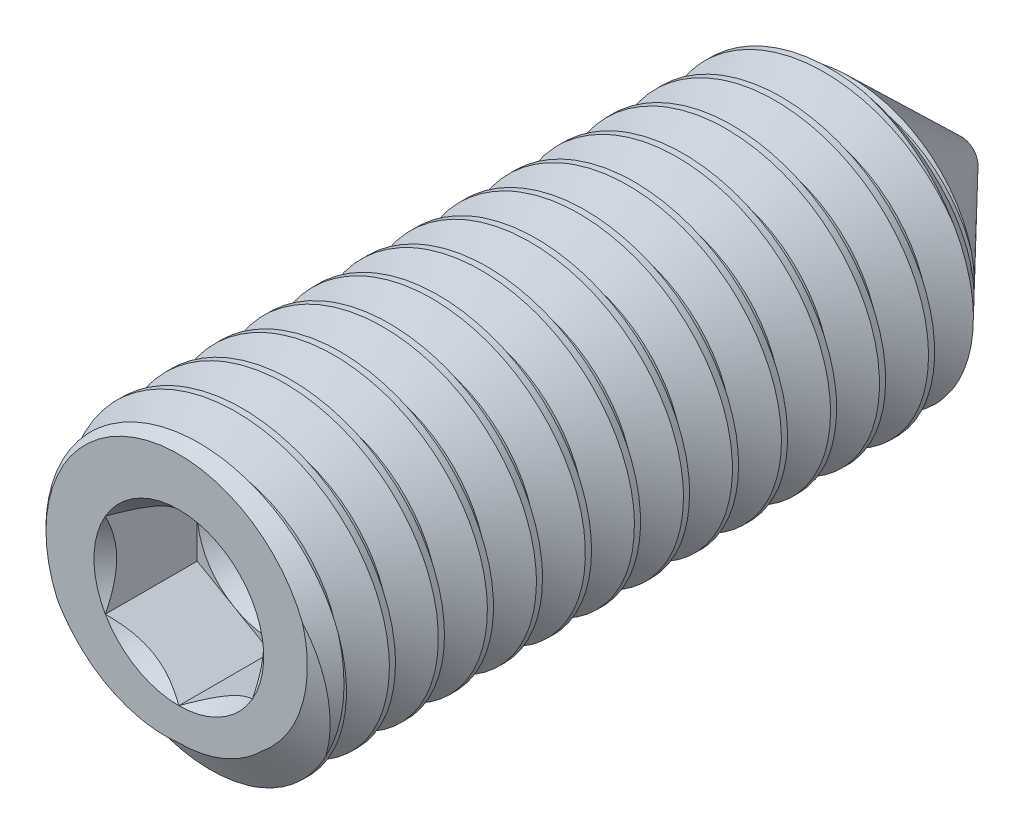
SolidWorks part; units mm, degrees
ref_plane "Front Plane" through (0, 0, 0) normal (0, 0, 1) x (1, 0, 0)
ref_plane "Top Plane" through (0, 0, 0) normal (0, 1, 0) x (1, 0, 0)
ref_plane "Right Plane" through (0, 0, 0) normal (1, 0, 0) x (0, 0, -1)
sketch "Sketch1" plane through (0, 0, 0) normal (1, 0, 0) x (0, 0, -1)
  line L0 (-6.35, 0) -> (6.35, 0) construction
  line L5 (-6.35, 2.413) -> (-6.35, -2.413) construction
  line L6 (6.35, 0.2413) -> (6.35, -0.2413) construction
  line L7 (6.35, 0.2413) -> (4.1783, 2.413) construction
  line L8 (6.35, -0.2413) -> (4.1783, -2.413) construction
  line L9 (-7.0941, 2.4989) -> (-6.3004, 2.4989) construction
  line L10 (-6.3004, 2.4989) -> (-6.6973, 1.8115) construction
  line L11 (-6.6973, 1.8115) -> (-7.0941, 2.4989) construction
  line L12 (-7.0445, 2.413) -> (-6.35, 2.413) construction
  line L13 (-6.7469, 1.8974) -> (-6.6477, 1.8974) construction
  line L14 (-6.6973, 1.8974) -> (-6.6973, 1.8115) construction
  line L15 (-6.6973, 2.413) -> (-6.6973, 2.4989) construction
  point P24 (-6.35, 1.1906)
  point P29 (-4.3656, -2.413)
  dimension "Screw Size Decimal Equivalent" = 4.826
  dimension "Length" = 12.7
  dimension "Cone Point Angle" = 90
  dimension "Drive Size" = 2.3813
  dimension "Approx. Point OD" = 0.4826
  dimension "Thread Pitch" = 0.7937
  dimension "Pitch/8" = 0.0992
  dimension "Thread Note" = 1.9844
sketch "Sketch2" plane through (0, 0, 0) normal (1, 0, 0) x (0, 0, -1)
  line L0 (-6.35, 0) -> (6.35, 0)
  line L1 (6.35, 0) -> (6.35, 0.2413)
  line L2 (6.35, 0.2413) -> (4.1783, 2.413)
  line L3 (4.1783, 2.413) -> (-6.35, 2.413)
  line L4 (-6.35, 2.413) -> (-6.35, 0)
revolve "Revolve1" add sketch "Sketch2" angle 360 about L0
chamfer "Chamfer1" distance 0.2619 angle 45 1 edges at (2.413, 0, 6.35)
sketch "Sketch3" plane through (0, 0, 6.35) normal (0, 0, 1) x (1, 0, 0)
  line L1 (0, -1.3748) -> (1.1906, -0.6874)
  line L2 (1.1906, -0.6874) -> (1.1906, 0.6874)
  line L3 (1.1906, 0.6874) -> (0, 1.3748)
  line L4 (0, 1.3748) -> (-1.1906, 0.6874)
  line L5 (-1.1906, 0.6874) -> (-1.1906, -0.6874)
  line L6 (-1.1906, -0.6874) -> (0, -1.3748)
  circle A0 centre (0, 0) radius 1.1906 construction
  circle A1 centre (0, 0) radius 2.413 construction
extrude "Cut-Extrude1" cut sketch "Sketch3" against normal blind 1.4883
sketch "Sketch4" plane through (0, 0, 6.35) normal (0, 0, 1) x (1, 0, 0)
  circle A0 centre (0, 0) radius 1.3748
extrude "Cut-Extrude2" cut sketch "Sketch4" against normal through all draft 45
sketch "Sketch5" plane through (0, 0, 4.8617) normal (0, 0, 1) x (1, 0, 0)
  line L0 (0, 1.3748) -> (1.1906, 0.6874) construction
  circle A0 centre (0, 0) radius 1.1906
extrude "Cut-Extrude3" cut sketch "Sketch5" against normal through all draft 45
fillet "Fillet1" radius 0.0483 1 edges at (0.2413, 0, -6.35)
sketch "Sketch6" plane through (0, 0, 6.35) normal (0, 0, -1) x (-1, 0, 0)
  circle A0 centre (0, 0) radius 2.413 construction
  circle A1 centre (0, 0) radius 2.413
sketch "Sketch10" plane through (0, 0, 0) normal (1, 0, 0) x (0, 0, -1)
  line L0 (3.7841, 0) -> (6.3359, 0) construction
  line L1 (-6.35, 0) -> (6.35, 0) construction
  line L2 (6.3359, 0) -> (6.3359, 0.2554)
  line L3 (6.3359, 0.2554) -> (4.1016, 2.413)
  line L5 (4.1016, 2.413) -> (3.7841, 2.413) construction
  line L6 (3.7841, 2.413) -> (3.7841, 0) construction
  line L7 (6.3359, 0) -> (6.6534, 0)
  line L8 (6.6534, 0) -> (6.6534, 2.413)
  line L9 (6.6534, 2.413) -> (4.1016, 2.413)
  dimension "D1" = 44
  dimension "D2" = 0.3175
revolve "Cut-Revolve6" cut sketch "Sketch10" angle 360 about L0
curve "Helix/Spiral1" pitch 0.7937 height 13.4937 radius 2.413 centre (0, 0, 6.35) axis (0, 0, -1) start towards (0, 1, 0)
sketch "Sketch7" plane through (0, 0, 0) normal (1, 0, 0) x (0, 0, -1)
  line L6 (-6.7469, 1.8974) -> (-6.6477, 1.8974)
  line L9 (-6.6477, 1.8974) -> (-6.3252, 2.456)
  line L10 (-6.3004, 2.4989) -> (-6.6973, 1.8115) construction
  line L11 (-6.3252, 2.456) -> (-7.0693, 2.456)
  line L12 (-6.6973, 1.8115) -> (-7.0941, 2.4989) construction
  line L13 (-7.0693, 2.456) -> (-6.7469, 1.8974)
  line L14 (-6.6973, 2.413) -> (-6.6973, 2.4989) construction
  point P10 (-6.6973, 2.456)
sweep "Cut-Sweep1" cut profiles "Sketch7" path "Helix/Spiral1" align with end faces yes
fillet "Fillet2" radius 0.0483 1 edges at (0.2554, 0, -6.3359)
equation "\"D1@Chamfer1\"=\"Thread Pitch@Sketch1\" * .33"
equation "\"D1@Cut-Extrude1\"=\"Drive Size@Sketch1\"*.625"
equation "\"D4@Helix/Spiral1\"=\"Thread Pitch@Sketch1\""
equation "\"D3@Helix/Spiral1\"=\"Length@Sketch1\"+\"Thread Pitch@Sketch1\""
equation "\"Approx. Point OD@Sketch1\"=\"Screw Size Decimal Equivalent@Sketch1\"*.1"
equation "\"Pitch/8@Sketch1\" = \"Thread Pitch@Sketch1\" / 8"
equation "\"Thread Note@Sketch1\"=\"Thread Pitch@Sketch1\"*2.5"
equation "\"D1@Sketch10\"=(\"Cone Point Angle@Sketch1\"*.5)-1"
equation "\"D2@Sketch10\"=\"Length@Sketch1\"*.025"
equation "\"D1@Fillet1\"=\"Approx. Point OD@sketch1\"*.1"
equation "\"D1@Fillet2\"=\"d1@fillet1\""
